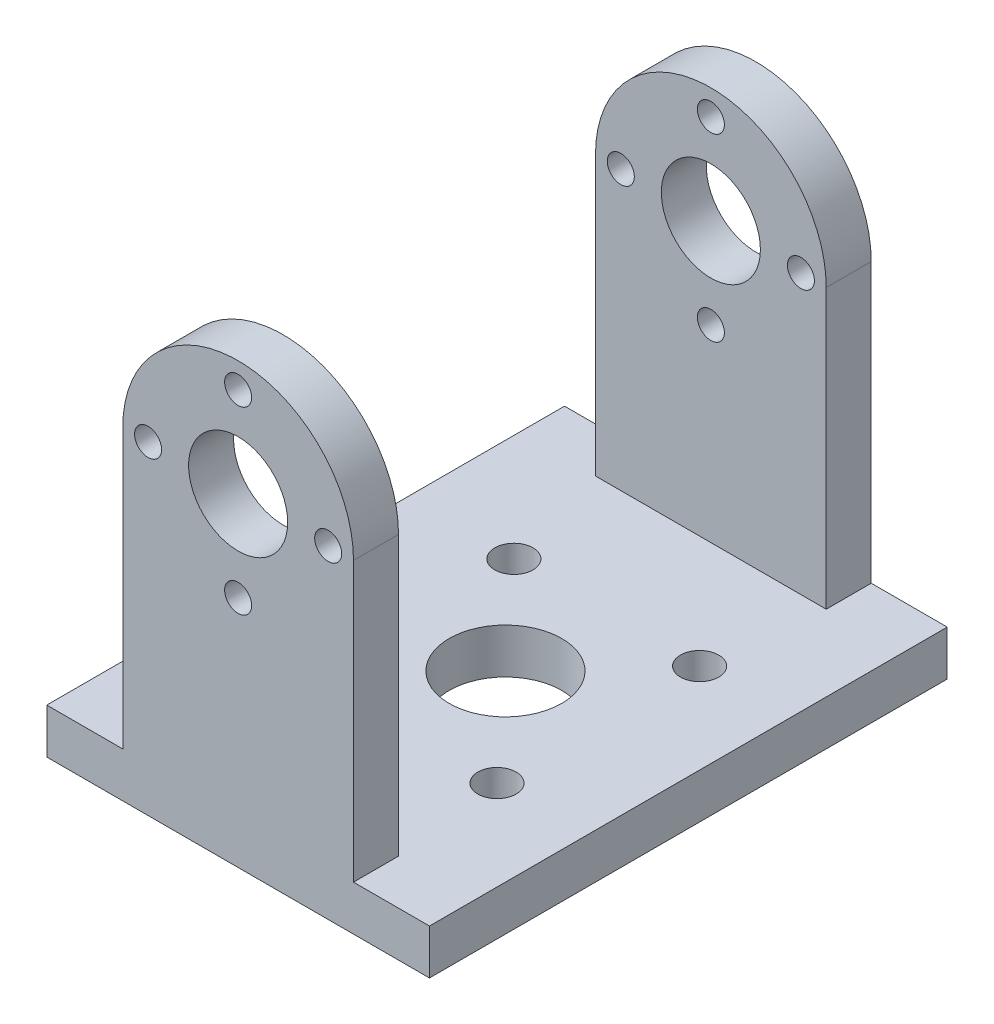
SolidWorks part; units mm, degrees
ref_plane "Front Plane" through (0, 0, 0) normal (0, 0, 1) x (1, 0, 0)
ref_plane "Top Plane" through (0, 0, 0) normal (0, 1, 0) x (1, 0, 0)
ref_plane "Right Plane" through (0, 0, 0) normal (1, 0, 0) x (0, 0, -1)
sketch "Sketch1" plane through (0, 0, 0) normal (0, 0, 1) x (1, 0, 0)
  line L0 (0, 0) -> (0, -68) construction
  line L1 (10.25, 0) -> (10.25, -68)
  line L2 (-10.25, 0) -> (-10.25, -68)
  line L3 (0, 0) -> (0, -68) construction
  line L4 (17, 0) -> (17, -68)
  line L5 (-17, 0) -> (-17, -68)
  line L7 (-10.25, -68) -> (10.25, -68)
  line L8 (-10.25, -68) -> (-10.25, -32.75)
  line L9 (-10.25, -32.75) -> (10.25, -32.75)
  line L10 (10.25, -68) -> (10.25, -32.75)
  line L11 (-17, -32.75) -> (17, -32.75)
  line L12 (-17, -32.75) -> (-17, -28.75)
  line L13 (-17, -28.75) -> (17, -28.75)
  line L14 (17, -32.75) -> (17, -28.75)
  line L15 (-10.25, -68) -> (10.25, -68)
  line L16 (-10.25, -68) -> (-10.25, -79.25)
  line L17 (-10.25, -79.25) -> (10.25, -79.25)
  line L18 (10.25, -68) -> (10.25, -79.25)
  arc A0 (10.25, 0) -> (-10.25, 0) centre (0, 0) ccw
  arc A1 (-10.25, -68) -> (10.25, -68) centre (0, -68) ccw
  arc A2 (17, 0) -> (-17, 0) centre (0, 0) ccw
  arc A3 (-17, -68) -> (17, -68) centre (0, -68) ccw
  circle A4 centre (0, 0) radius 8
  circle A5 centre (0, 8) radius 1.2
  circle A6 centre (8, 0) radius 1.2
  circle A7 centre (0, -8) radius 1.2
  circle A8 centre (-8, 0) radius 1.2
  circle A9 centre (0, -68) radius 10.25
  circle A10 centre (0, 0) radius 4.4
  point P3 (0, -34)
  point P10 (0, -34)
  point P28 (0, 0)
  dimension "D2" = 10.25
  dimension "D3" = 17
  dimension "D4" = 16
  dimension "D5" = 2.4
  dimension "D10" = 8.8
  dimension "D1" = 68
  dimension "D7" = 35.25
  dimension "D8" = 4
  dimension "D9" = 11.25
  dimension "D6" = 4
extrude "Boss-Extrude1" add sketch "Sketch1" along normal blind 4 contours A8 A4 A7 A6 A5 A10 | L1 A0 L2 L13 A8 A4 A5 A6 A7 region at (0, -14.2541, 0) region at (6.5763, 0, 0)
sketch "Sketch3" plane through (0, -28.75, 0) normal (0, -1, 0) x (-1, 0, 0)
  line L21 (-10.25, -4) -> (-10.25, 0) construction
  line L22 (-17, 0) -> (17, 0)
  line L23 (-17, 0) -> (-17, -46)
  line L24 (-17, -46) -> (17, -46)
  line L25 (17, 0) -> (17, -46)
  line L28 (10.25, 0) -> (-10.25, 0) construction
  circle A0 centre (-0.75, -23) radius 5
  circle A1 centre (-9, -14) radius 1.7
  circle A2 centre (7.5, -14) radius 1.7
  circle A3 centre (7.5, -32) radius 1.7
  circle A4 centre (-9, -32) radius 1.7
  dimension "D3" = 3.4
  dimension "D4" = 9
  dimension "D5" = 8.25
  dimension "D8" = 23
  dimension "D10" = 8.25
  dimension "D11" = 9
  dimension "D1" = 34
  dimension "D2" = 6.75
  dimension "D9" = 46
  dimension "D12" = 0
  dimension "D6" = 2
  dimension "D7" = 2
extrude "Boss-Extrude3" add sketch "Sketch3" against normal blind 4
ref_plane "Plane1" through (0, 0, 23) normal (0, 0, 1) x (1, 0, 0)
mirror "Mirror1" about plane through (0, 0, 23) normal (0, 0, 1) of "Boss-Extrude1"
